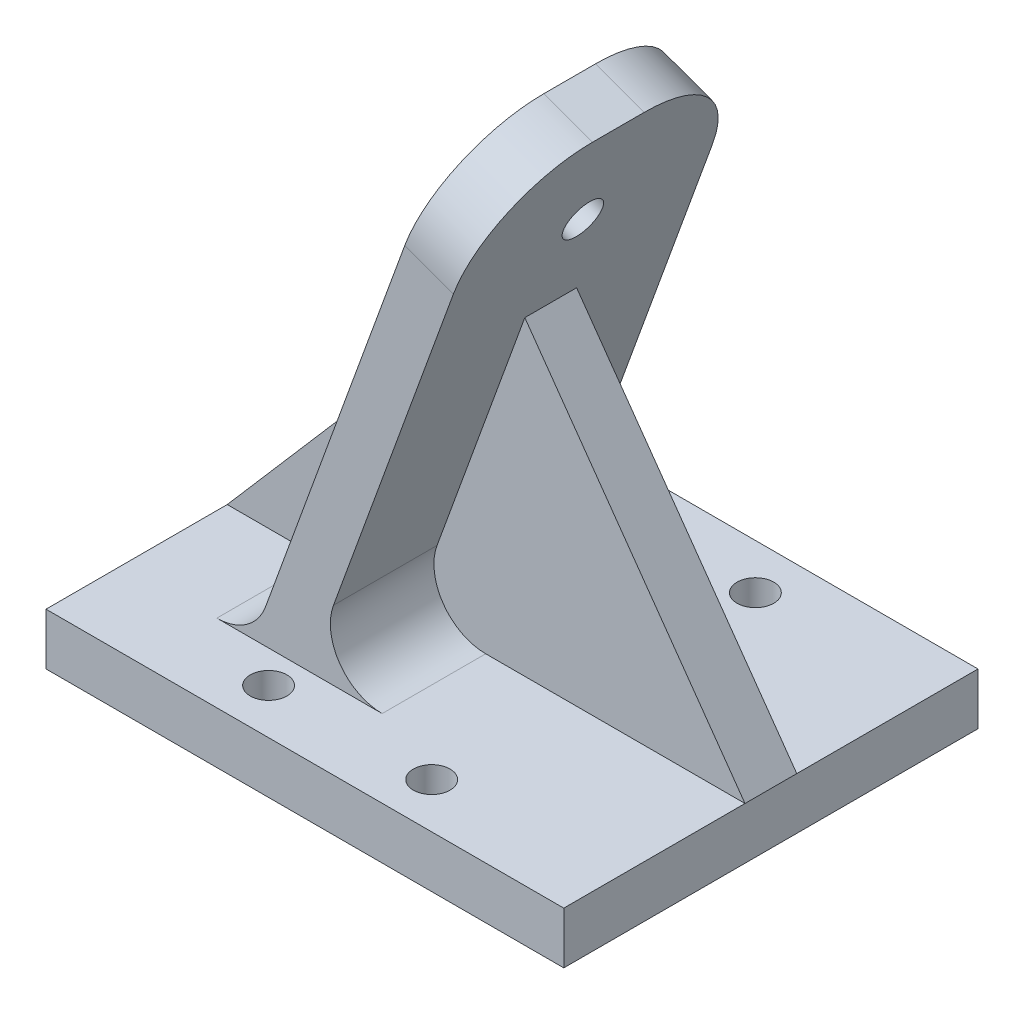
SolidWorks part; units mm, degrees
material "PLA Black"
ref_plane "Front Plane" through (0, 0, 0) normal (0, 0, 1) x (1, 0, 0)
ref_plane "Top Plane" through (0, 0, 0) normal (0, 1, 0) x (1, 0, 0)
ref_plane "Right Plane" through (0, 0, 0) normal (1, 0, 0) x (0, 0, -1)
sketch "Sketch1" plane through (0, 0, 0) normal (0, 1, 0) x (1, 0, 0)
  line L1 (-31.75, -25.4) -> (31.75, -25.4)
  line L2 (-31.75, -25.4) -> (-31.75, 25.4)
  line L3 (-31.75, 25.4) -> (31.75, 25.4)
  line L4 (31.75, -25.4) -> (31.75, 25.4)
  line L5 (-31.75, -25.4) -> (31.75, 25.4) construction
  line L6 (-31.75, 25.4) -> (31.75, -25.4) construction
  point P0 (0, 0)
  dimension "D1" = 63.5
  dimension "D2" = 50.8
extrude "Boss-Extrude1" add sketch "Sketch1" along normal blind 6.35
sketch "Sketch2" plane through (0, 0, 0) normal (0, 0, 1) x (1, 0, 0)
  line L0 (-11.43, 0) -> (13.0366, 67.2214)
  line L1 (-11.43, 0) -> (-17.397, 2.1718)
  line L2 (13.0366, 67.2214) -> (7.0695, 69.3932)
  line L3 (-17.397, 2.1718) -> (7.0695, 69.3932)
  line L4 (-11.43, 0) -> (7.0695, 69.3932) construction
  line L5 (13.0366, 67.2214) -> (-17.397, 2.1718) construction
  line L6 (31.75, 6.35) -> (31.75, 0) construction
  line L7 (-31.75, 0) -> (31.75, 0) construction
  point P1 (-2.1802, 34.6966)
  dimension "D1" = 20
  dimension "D2" = 50.8
  dimension "D3" = 11.43
extrude "Boss-Extrude2" add sketch "Sketch2" against normal mid plane 31.75
fillet "Fillet1" radius 12.7 2 edges at (10.0531, 68.3073, 15.875) (10.0531, 68.3073, -15.875)
sketch "Sketch5" plane through (-16.06, 5.8454, 0) normal (-0.9397, 0.342, 0) x (0, 0, 1)
  line L0 (-3.175, 67.6262) -> (3.175, 67.6262) construction
  circle A0 centre (0, 54.9262) radius 2.413
  point P6 (0, 67.6262)
  dimension "D1" = 4.826
  dimension "D2" = 12.7
fillet "Fillet2" radius 6.35 2 edges at (-15.8763, 6.35, 0) (-9.1188, 6.35, 0)
sketch "Sketch7" plane through (0, 0, 0) normal (0, 0, 1) x (1, 0, 0)
  line L0 (4.7485, 44.45) -> (31.75, 6.35)
  line L2 (-31.75, 6.35) -> (31.75, 6.35) construction
  line L3 (-31.75, 6.35) -> (-20.3226, 6.35)
  line L7 (-31.75, 6.35) -> (-4.3203, 38.1)
  line L8 (2.7259, 57.4591) -> (-14.3556, 10.5282) construction
  line L10 (-4.3203, 38.1) -> (-14.3556, 10.5282)
  line L12 (-0.05, 6.35) -> (31.75, 6.35)
  line L13 (-6.0171, 14.8718) -> (4.7485, 44.45)
  line L14 (-6.0171, 14.8718) -> (8.6929, 55.2873) construction
  arc A0 (-6.0171, 14.8718) -> (-0.05, 6.35) centre (-0.05, 12.7) ccw construction
  arc A4 (-20.3226, 6.35) -> (-14.3556, 10.5282) centre (-20.3226, 12.7) ccw construction
  arc A5 (-6.0171, 14.8718) -> (-0.05, 6.35) centre (-0.05, 12.7) ccw
  arc A6 (-20.3226, 6.35) -> (-14.3556, 10.5282) centre (-20.3226, 12.7) ccw
  dimension "D1" = 31.75
  dimension "D2" = 38.1
extrude "Boss-Extrude5" add sketch "Sketch7" along normal mid plane 6.35
extrude "Cut-Extrude3" cut sketch "Sketch5" against normal through all
sketch "Sketch8" plane through (0, 6.35, 0) normal (0, 1, 0) x (1, 0, 0)
  line L4 (-10, -19.85) -> (10, 19.85) construction
  circle A0 centre (10, -19.85) radius 2.25
  circle A1 centre (10, 19.85) radius 2.25
  circle A2 centre (-10, 19.85) radius 2.25
  circle A3 centre (-10, -19.85) radius 2.25
  point P8 (0, 0)
  point P9 (-10.0923, 40.4891)
  point P10 (-19.8928, 21.5024)
  dimension "D2" = 4.5
  dimension "D1" = 39.7
  dimension "D5" = 20
extrude "Cut-Extrude4" cut sketch "Sketch8" against normal through all
